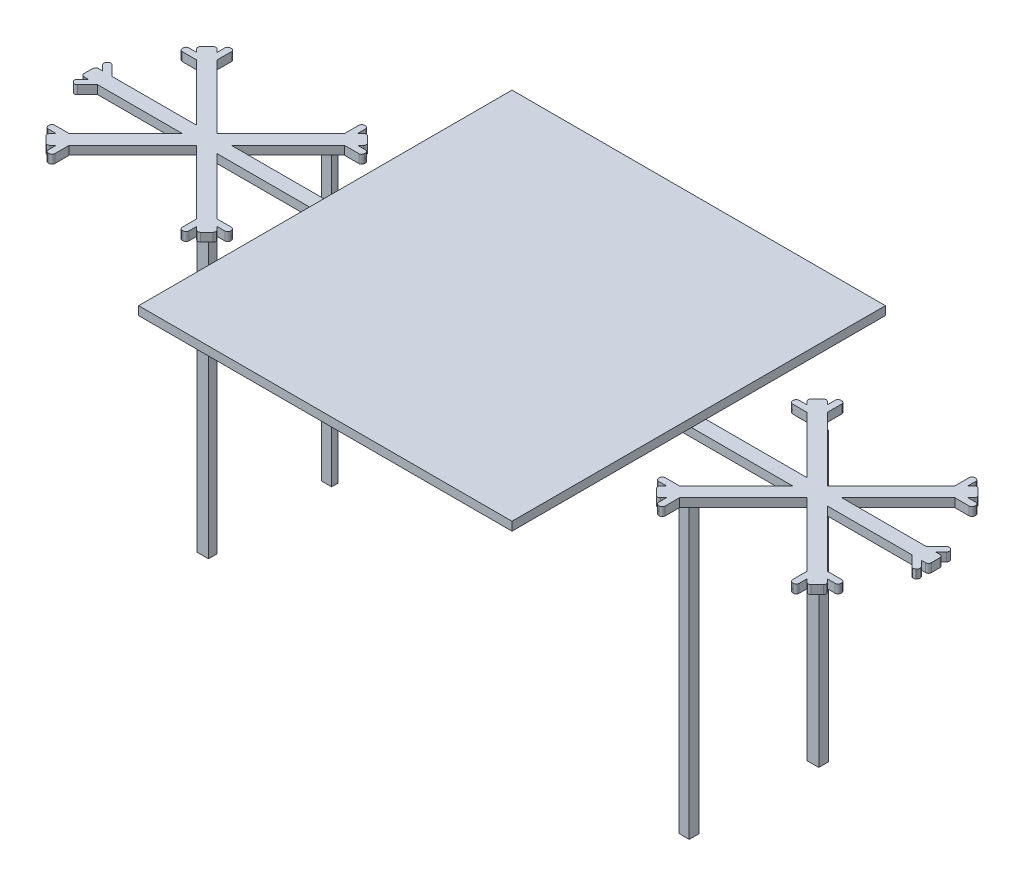
SolidWorks part; units mm, degrees
material "ABS"
ref_plane "Front" through (0, 0, 0) normal (0, 0, 1) x (1, 0, 0)
ref_plane "Top" through (0, 0, 0) normal (0, 1, 0) x (1, 0, 0)
ref_plane "Right" through (0, 0, 0) normal (1, 0, 0) x (0, 0, -1)
sketch "Sketch1" plane through (0, 0, 0) normal (0, 1, 0) x (1, 0, 0)
  line L1 (-65, -65) -> (65, -65)
  line L2 (-65, -65) -> (-65, 65)
  line L3 (-65, 65) -> (65, 65)
  line L4 (65, -65) -> (65, 65)
  line L5 (-65, -65) -> (65, 65) construction
  line L6 (-65, 65) -> (65, -65) construction
  point P0 (0, 0)
  dimension "D1" = 130
  dimension "D2" = 130
extrude "Boss-Extrude1" add sketch "Sketch1" along normal blind 3
sketch "Sketch2" plane through (0, 0, 0) normal (0, -1, 0) x (1, 0, 0)
  line L0 (-147.4984, 0.0016) -> (-141.774, 0.0016) construction
  line L1 (-147.5016, -2.4984) -> (-144.9984, -2.4984)
  line L3 (-147.5016, 2.5016) -> (-144.9984, 2.5016)
  line L4 (147.5016, -2.4984) -> (147.5016, 2.5016)
  line L5 (-130.7147, 28.0003) -> (-132.4825, 29.768)
  line L6 (107.9536, -1.8297) -> (107.9558, -1.8298) construction
  line L7 (-134.2503, 24.4647) -> (-136.018, 26.2325)
  line L9 (104.4822, 1.7678) -> (104.4854, 1.7709)
  line L10 (112.2871, 2.5016) -> (131.9725, 22.1869)
  line L11 (132.4825, 29.768) -> (136.018, 26.2325)
  line L17 (128.4369, 25.7225) -> (128.4369, 31.7225)
  line L18 (128.4369, 31.7225) -> (130.7147, 31.7225)
  line L19 (130.7147, 31.7225) -> (130.7147, 28.0003)
  line L20 (130.7147, 28.0003) -> (134.2503, 24.4647) construction
  line L21 (128.4369, 25.7225) -> (131.9725, 22.1869) construction
  line L22 (134.2503, 24.4647) -> (137.9725, 24.4647)
  line L23 (137.9725, 24.4647) -> (137.9725, 22.1869)
  line L24 (137.9725, 22.1869) -> (131.9725, 22.1869)
  line L25 (0, 0) -> (0, -65) construction
  line L26 (65, -65) -> (-65, -65) construction
  line L27 (-141.774, 2.5016) -> (-112.2871, 2.5016)
  line L28 (141.774, 2.5016) -> (146.0166, 6.7442)
  line L29 (146.0166, 6.7442) -> (147.6289, 5.132)
  line L30 (147.6289, 5.132) -> (144.9984, 2.5016)
  line L31 (141.774, -2.4984) -> (146.0166, -6.7411)
  line L32 (146.0166, -6.7411) -> (147.6289, -5.1289)
  line L33 (147.6289, -5.1289) -> (144.9984, -2.4984)
  line L34 (144.9984, 2.5016) -> (144.9984, -2.4984) construction
  line L35 (141.774, 2.5016) -> (141.774, -2.4984) construction
  line L36 (74.5291, 22.1885) -> (80.5291, 22.1885)
  line L37 (74.5291, 24.4663) -> (74.5291, 22.1885)
  line L38 (78.2513, 24.4663) -> (74.5291, 24.4663)
  line L39 (81.7853, 31.7225) -> (81.7853, 28.0003)
  line L40 (84.0631, 25.7225) -> (84.0631, 31.7225)
  line L41 (84.0631, 31.7225) -> (81.7853, 31.7225)
  line L42 (100.2161, 2.5016) -> (80.5291, 22.1885)
  line L43 (80.0175, 29.768) -> (76.4835, 26.2341)
  line L46 (128.4369, -25.7193) -> (128.4369, -31.7193)
  line L47 (130.7147, -31.7193) -> (130.7147, -27.9971)
  line L48 (128.4369, -31.7193) -> (130.7147, -31.7193)
  line L49 (134.2519, -24.4632) -> (137.9725, -24.4616)
  line L50 (137.9725, -24.4616) -> (137.9725, -22.1837)
  line L51 (137.9725, -22.1837) -> (131.9725, -22.1837)
  line L52 (112.2871, -2.4984) -> (131.9725, -22.1837)
  line L53 (132.4825, -29.7649) -> (136.018, -26.2293)
  line L54 (-81.7853, 28.0003) -> (-80.0175, 29.768)
  line L55 (-78.2513, 24.4663) -> (-76.4835, 26.2341)
  line L56 (84.0631, -25.7193) -> (84.0631, -31.7193)
  line L57 (84.0631, -31.7193) -> (81.7853, -31.7193)
  line L58 (81.7853, -31.7193) -> (81.7853, -27.9971)
  line L59 (74.5291, -22.1853) -> (80.5291, -22.1853)
  line L60 (74.5291, -24.4632) -> (74.5291, -22.1853)
  line L61 (78.2513, -24.4632) -> (74.5291, -24.4632)
  line L62 (-78.2513, -24.4632) -> (-76.4835, -26.2309)
  line L63 (-81.7853, -27.9971) -> (-80.0175, -29.7649)
  line L64 (80.0175, -29.7649) -> (76.4835, -26.2309)
  line L65 (100.2161, -2.4984) -> (80.5291, -22.1853)
  line L66 (-141.774, 2.5016) -> (-141.774, -2.4984) construction
  line L67 (-144.9984, 2.5016) -> (-144.9984, -2.4984) construction
  line L68 (-130.7147, -27.9971) -> (-132.4825, -29.7649)
  line L69 (-128.4369, 25.7225) -> (-131.9725, 22.1869) construction
  line L70 (-130.7147, 28.0003) -> (-134.2503, 24.4647) construction
  line L72 (-100.2161, -2.4984) -> (-80.5291, -22.1853)
  line L73 (-80.0175, -29.7649) -> (-76.4835, -26.2309)
  line L74 (-106.25, -3.5324) -> (-84.0631, -25.7193)
  line L75 (141.774, 0.0016) -> (147.5016, 0.0016) construction
  line L76 (-78.2513, -24.4632) -> (-74.5291, -24.4632)
  line L77 (-74.5291, -24.4632) -> (-74.5291, -22.1853)
  line L78 (-74.5291, -22.1853) -> (-80.5291, -22.1853)
  line L79 (-81.7853, -31.7193) -> (-81.7853, -27.9971)
  line L80 (-84.0631, -31.7193) -> (-81.7853, -31.7193)
  line L81 (-84.0631, -25.7193) -> (-84.0631, -31.7193)
  line L82 (107.9536, 1.8297) -> (107.9558, 1.8298) construction
  line L83 (-106.25, -3.5324) -> (-128.4369, -25.7193)
  line L84 (-132.4825, -29.7649) -> (-136.018, -26.2293)
  line L85 (-112.2871, -2.4984) -> (-131.9725, -22.1837)
  line L86 (-137.9725, -22.1837) -> (-131.9725, -22.1837)
  line L87 (-137.9725, -24.4616) -> (-137.9725, -22.1837)
  line L88 (-134.2519, -24.4632) -> (-137.9725, -24.4616)
  line L89 (-128.4369, -31.7193) -> (-130.7147, -31.7193)
  line L90 (-130.7147, -31.7193) -> (-130.7147, -27.9971)
  line L91 (-128.4369, -25.7193) -> (-128.4369, -31.7193)
  line L93 (-106.25, 3.5355) -> (-84.0631, 25.7225)
  line L94 (-80.0175, 29.768) -> (-76.4835, 26.2341)
  line L95 (112.2871, -2.4984) -> (141.774, -2.4984)
  line L96 (-84.0631, 31.7225) -> (-81.7853, 31.7225)
  line L97 (-84.0631, 25.7225) -> (-84.0631, 31.7225)
  line L98 (-81.7853, 31.7225) -> (-81.7853, 28.0003)
  line L99 (-78.2513, 24.4663) -> (-74.5291, 24.4663)
  line L100 (-74.5291, 24.4663) -> (-74.5291, 22.1885)
  line L101 (-74.5291, 22.1885) -> (-80.5291, 22.1885)
  line L102 (-147.6289, -5.1289) -> (-144.9984, -2.4984)
  line L103 (-146.0166, -6.7411) -> (-147.6289, -5.1289)
  line L104 (-141.774, -2.4984) -> (-146.0166, -6.7411)
  line L105 (-147.6289, 5.132) -> (-144.9984, 2.5016)
  line L106 (-146.0166, 6.7442) -> (-147.6289, 5.132)
  line L107 (-141.774, 2.5016) -> (-146.0166, 6.7442)
  line L108 (-137.9725, 22.1869) -> (-131.9725, 22.1869)
  line L109 (-137.9725, 24.4647) -> (-137.9725, 22.1869)
  line L110 (-134.2503, 24.4647) -> (-137.9725, 24.4647)
  line L111 (-130.7147, 31.7225) -> (-130.7147, 28.0003)
  line L112 (-128.4369, 31.7225) -> (-130.7147, 31.7225)
  line L113 (-128.4369, 25.7225) -> (-128.4369, 31.7225)
  line L114 (-132.4825, 29.768) -> (-136.018, 26.2325)
  line L115 (106.25, -3.5324) -> (84.0631, -25.7193)
  line L116 (-134.2519, -24.4632) -> (-136.018, -26.2293)
  line L117 (106.25, -3.5324) -> (128.4369, -25.7193)
  line L118 (-141.774, -2.4984) -> (-112.2871, -2.4984)
  line L119 (-147.5016, -2.4984) -> (-147.5016, 2.5016)
  line L120 (81.7853, 28.0003) -> (80.0175, 29.768)
  line L121 (78.2513, 24.4663) -> (76.4835, 26.2341)
  line L122 (-112.2871, 2.5016) -> (-131.9725, 22.1869)
  line L123 (130.7147, 28.0003) -> (132.4825, 29.768)
  line L124 (-106.25, 3.5355) -> (-128.4369, 25.7225)
  line L125 (-100.2161, 2.5016) -> (100.2161, 2.5016)
  line L126 (-100.2161, 2.5016) -> (-80.5291, 22.1885)
  line L127 (134.2503, 24.4647) -> (136.018, 26.2325)
  line L128 (-100.2161, -2.4984) -> (100.2161, -2.4984)
  line L130 (106.25, 3.5355) -> (84.0631, 25.7225)
  line L131 (112.2871, 2.5016) -> (141.774, 2.5016)
  line L132 (106.25, 3.5355) -> (128.4369, 25.7225)
  line L133 (144.9984, 2.5016) -> (147.5016, 2.5016)
  line L134 (144.9984, -2.4984) -> (147.5016, -2.4984)
  line L135 (134.2519, -24.4632) -> (136.018, -26.2293)
  line L136 (130.7147, -27.9971) -> (132.4825, -29.7649)
  line L137 (78.2513, -24.4632) -> (76.4835, -26.2309)
  line L138 (81.7853, -27.9971) -> (80.0175, -29.7649)
  arc A4 (104.4854, 1.7709) -> (104.4822, 1.7678) centre (106.2516, 0.0016) ccw
  point P0 (0, 0)
  point P11 (-193.212, 33.1965)
  point P13 (106.2516, 0.0016)
  point P17 (-121.8101, 67.8097)
  point P20 (-193.9403, 24.9676)
  point P127 (-106.2516, 0.0016)
  line M45 (65, -65) -> (65, 65)
  line M47 (-65, 65) -> (-65, -65)
  dimension "D3" = 41.25
extrude "Boss-Extrude3" add sketch "Sketch2" along normal blind 3 contours L128 L125 M47 M45 | L138 L58 L57 L56 L115 L117 L46 L48 L47 L136 L53 L135 L49 L50 L51 L52 L95 L31 L32 L33 L134 L4 L133 L30 L29 L28 L131 L10 L24 L23 L22 L127 L11 L123 L19 L18 L17 L132 L130 L40 L41 L39 L120 L43 L121 L38 L37 L36 L42 L125 M45 | L72 L128 L125 L126 L101 L100 L99 L55 L94 L54 L98 L96 L97 L93 L124 L113 L112 L111 L5 L114 L7 L110 L109 L108 L122 L27 L107 L106 L105 L3 L119 L1 L102 L103 L104 L118 L85 L86 L87 L88 L116 L84 L68 L90 L89 L91 L83 L74 L81 L80 M47 region at (-106.944, 0, 0.0015) region at (0, 0, 0.0016) region at (106.944, 0, 0.0015)
fillet "Fillet1" radius 1 60 edges at (-74.5291, -1.5, -22.1853) (-74.5291, -1.5, -24.4632) (-76.4835, -1.5, -26.2309) (-80.0175, -1.5, -29.7649) (-81.7853, -1.5, -31.7193) (-84.0631, -1.5, -31.7193) (-74.5291, -1.5, 22.1885) (-74.5291, -1.5, 24.4663) (-76.4835, -1.5, 26.2341) (-80.0175, -1.5, 29.768) (-81.7853, -1.5, 31.7225) (-84.0631, -1.5, 31.7225) (-128.4369, -1.5, 31.7225) (-130.7147, -1.5, 31.7225) (-132.4825, -1.5, 29.768) (-136.018, -1.5, 26.2325) (-137.9725, -1.5, 22.1869) (-137.9725, -1.5, 24.4647) (-128.4369, -1.5, -31.7193) (-130.7147, -1.5, -31.7193) (-132.4825, -1.5, -29.7649) (-136.018, -1.5, -26.2293) (-137.9725, -1.5, -24.4616) (-137.9725, -1.5, -22.1837) (-146.0166, -1.5, 6.7442) (-147.6289, -1.5, 5.132) (-147.5016, -1.5, 2.5016) (-147.5016, -1.5, -2.4984) (-147.6289, -1.5, -5.1289) (-146.0166, -1.5, -6.7411) (84.0631, -1.5, -31.7193) (81.7853, -1.5, -31.7193) (80.0175, -1.5, -29.7649) (76.4835, -1.5, -26.2309) (74.5291, -1.5, -22.1853) (74.5291, -1.5, -24.4632) (74.5291, -1.5, 22.1885) (74.5291, -1.5, 24.4663) (76.4835, -1.5, 26.2341) (80.0175, -1.5, 29.768) (84.0631, -1.5, 31.7225) (81.7853, -1.5, 31.7225) (128.4369, -1.5, 31.7225) (130.7147, -1.5, 31.7225) (132.4825, -1.5, 29.768) (136.018, -1.5, 26.2325) (137.9725, -1.5, 24.4647) (137.9725, -1.5, 22.1869) (146.0166, -1.5, 6.7442) (147.6289, -1.5, 5.132) (147.5016, -1.5, 2.5016) (147.5016, -1.5, -2.4984) (147.6289, -1.5, -5.1289) (146.0166, -1.5, -6.7411) (137.9725, -1.5, -22.1837) (137.9725, -1.5, -24.4616) (136.018, -1.5, -26.2293) (132.4825, -1.5, -29.7649) (130.7147, -1.5, -31.7193) (128.4369, -1.5, -31.7193)
sketch "Sketch3" plane through (0, -3, 0) normal (0, -1, 0) x (1, 0, 0)
  line L20 (-100.2161, 2.5016) -> (-80.5291, 22.1885) construction
  line L27 (-86.4752, 23.1678) -> (-82.5095, 23.1678)
  line L28 (-86.4752, 23.1678) -> (-86.4752, 20.2082)
  line L29 (-86.4752, 20.2082) -> (-82.5095, 20.2082)
  line L30 (-82.5095, 23.1678) -> (-82.5095, 20.2082)
  line L31 (-86.4752, 23.1678) -> (-82.5095, 20.2082) construction
  line L32 (-86.4752, 20.2082) -> (-82.5095, 23.1678) construction
  line L33 (-100.2161, -2.4984) -> (-80.5291, -22.1853) construction
  line L34 (-86.2213, -22.1837) -> (-82.7617, -22.1837)
  line L35 (-86.2213, -22.1837) -> (-86.2213, -19.9528)
  line L36 (-86.2213, -19.9528) -> (-82.7617, -19.9528)
  line L37 (-82.7617, -22.1837) -> (-82.7617, -19.9528)
  line L38 (-86.2213, -22.1837) -> (-82.7617, -19.9528) construction
  line L39 (-86.2213, -19.9528) -> (-82.7617, -22.1837) construction
  line L40 (100.2161, -2.4984) -> (80.5291, -22.1853) construction
  line L41 (86.6426, -23.4993) -> (82.556, -23.4993)
  line L42 (86.6426, -23.4993) -> (86.6426, -20.1585)
  line L43 (86.6426, -20.1585) -> (82.556, -20.1585)
  line L44 (82.556, -23.4993) -> (82.556, -20.1585)
  line L45 (86.6426, -23.4993) -> (82.556, -20.1585) construction
  line L46 (86.6426, -20.1585) -> (82.556, -23.4993) construction
  line L48 (82.3092, 24.0897) -> (85.7911, 24.0897)
  line L49 (82.3092, 24.0897) -> (82.3092, 20.7509)
  line L50 (82.3092, 20.7509) -> (85.7911, 20.7509)
  line L51 (85.7911, 24.0897) -> (85.7911, 20.7509)
  line L52 (82.3092, 24.0897) -> (85.7911, 20.7509) construction
  line L53 (82.3092, 20.7509) -> (85.7911, 24.0897) construction
  point P24 (-84.4923, 21.688)
  point P31 (-84.4915, -21.0682)
  point P38 (84.5993, -21.8289)
  point P45 (84.0502, 22.4203)
extrude "Boss-Extrude4" add sketch "Sketch3" along normal blind 100
